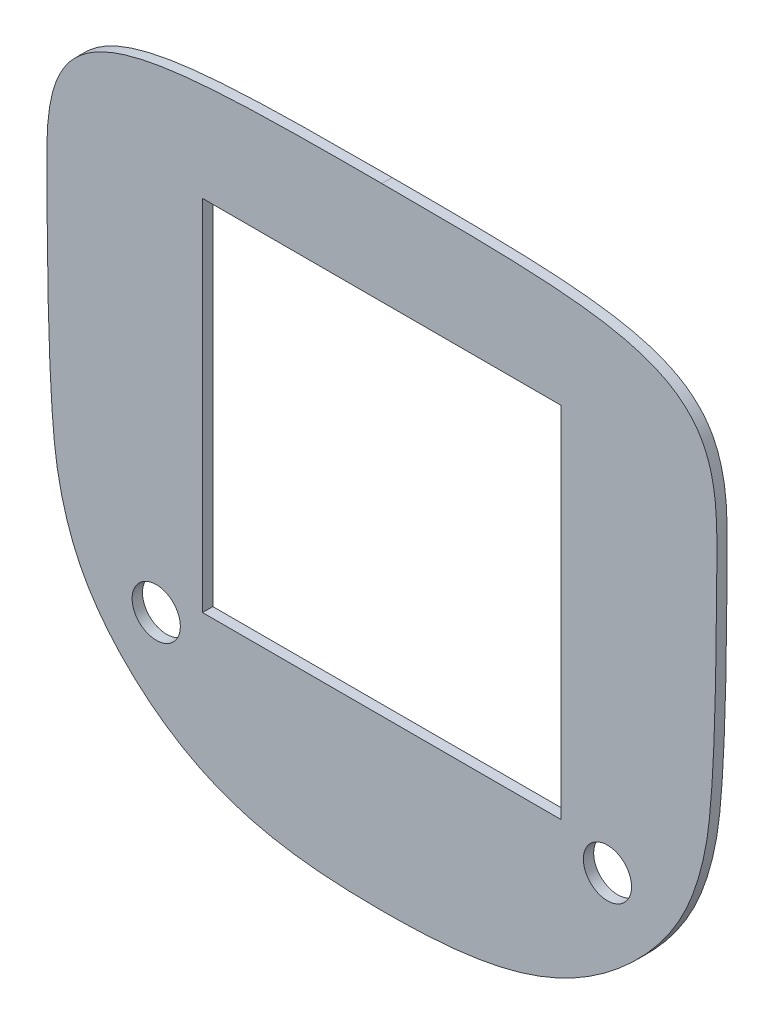
SolidWorks part; units mm, degrees
ref_plane "Front Plane" through (0, 0, 0) normal (0, 0, 1) x (1, 0, 0)
ref_plane "Top Plane" through (0, 0, 0) normal (0, 1, 0) x (1, 0, 0)
ref_plane "Right Plane" through (0, 0, 0) normal (1, 0, 0) x (0, 0, -1)
ref_plane "Plane1" through (0, 0, 100) normal (0, 0, -1) x (-1, 0, 0)
sketch "Sketch1" plane through (0, 0, 100) normal (0, 0, -1) x (-1, 0, 0)
  line L0 (0, 109.7056) -> (0, -73.1371) construction
  line L2 (-52.07, 79.9412) -> (52.07, 79.9412)
  line L3 (-52.07, 79.9412) -> (-52.07, -24.1988)
  line L4 (-52.07, -24.1988) -> (52.07, -24.1988)
  line L5 (52.07, 79.9412) -> (52.07, -24.1988)
  line L6 (-52.07, 79.9412) -> (52.07, -24.1988) construction
  line L7 (-52.07, -24.1988) -> (52.07, 79.9412) construction
  circle A0 centre (-65.5, -30.8878) radius 7
  circle A1 centre (65.5, -30.8878) radius 7
  spline S0 degree 3 poles (120.0442, -3042.1017) (366.3134, 126.0675) (163.9693, -79.8175) (-13.4407, -72.8192) (-16.7834, -72.6088) (-23.4392, -71.9641) (-26.7521, -71.5296) (-33.3376, -70.3562) (-36.61, -69.6165) (-40.6674, -68.4431) (-41.4772, -68.196) (-43.0934, -67.6755) (-43.9008, -67.4017) (-46.31, -66.5418) (-47.8892, -65.9204) (-52.5445, -63.9094) (-55.537, -62.3708) (-61.3063, -58.9085) (-64.0845, -56.9872) (-67.4275, -54.3545) (-68.0901, -53.8159) (-69.3935, -52.723) (-70.0355, -52.1678) (-71.9328, -50.4771) (-73.1598, -49.3164) (-76.728, -45.7341) (-78.9589, -43.2145) (-82.0396, -39.1995) (-83.0214, -37.8212) (-84.8841, -34.9749) (-85.7674, -33.501) (-88.2046, -29.0237) (-89.5634, -25.9428) (-91.2398, -21.1907) (-91.7446, -19.5872) (-92.6604, -16.3463) (-93.0697, -14.7082) (-93.7952, -11.3985) (-94.1118, -9.723) (-94.6517, -6.3658) (-94.8768, -4.683) (-95.2393, -1.3093) (-95.3906, 0.3804) (-95.6676, 3.7621) (-95.7898, 5.4545) (-96.0069, 8.8417) (-96.1016, 10.5367) (-96.2755, 13.928) (-96.3542, 15.6244) (-96.5678, 20.7138) (-96.6807, 24.1076) (-96.9534, 34.291) (-97.0459, 41.0827) (-97.1493, 51.27) (-97.1785, 54.6658) (-97.2277, 59.7595) (-97.2458, 61.4574) (-97.2868, 64.8533) (-97.3103, 66.5515) (-97.2904, 69.9429) (-97.2559, 71.6367) (-97.0958, 75.0177) (-96.9726, 76.705) (-96.5853, 80.0691) (-96.3204, 81.7458) (-95.8548, 83.8317) (-95.7548, 84.2484) (-95.5396, 85.0806) (-95.4241, 85.4969) (-95.0548, 86.7335) (-94.7779, 87.544) (-93.8439, 89.9287) (-93.0837, 91.4561) (-91.9173, 93.2675) (-91.6726, 93.6258) (-91.167, 94.3236) (-90.9058, 94.6639) (-90.0972, 95.6599) (-89.5251, 96.2905) (-88.3172, 97.4873) (-87.6813, 98.0535) (-86.6823, 98.8572) (-86.3418, 99.1176) (-85.6463, 99.6235) (-85.2903, 99.8697) (-83.4921, 101.0547) (-81.9897, 101.864) (-78.8918, 103.2801) (-77.2954, 103.8853) (-74.8499, 104.6822) (-74.0257, 104.9295) (-72.3778, 105.3877) (-71.5521, 105.5993) (-69.0705, 106.1898) (-67.4103, 106.5251) (-64.0815, 107.1133) (-62.4129, 107.3654) (-57.3979, 108.0286) (-54.0423, 108.3496) (-47.3172, 108.8523) (-43.9476, 109.0331) (-37.2, 109.3116) (-33.822, 109.4086) (-27.0609, 109.5527) (-23.6778, 109.5995) (253.3858, 112.2518) (527.5922, 23.6128) (784.5058, 2939.6821) knots -1.59089 -1.59089 -1.59089 -1.59089 0.03125 0.03125 0.0625 0.0625 0.09375 0.09375 0.125 0.125 0.132812 0.132812 0.140625 0.140625 0.15625 0.15625 0.1875 0.1875 0.21875 0.21875 0.226562 0.226562 0.234375 0.234375 0.25 0.25 0.28125 0.28125 0.296875 0.296875 0.3125 0.3125 0.34375 0.34375 0.359375 0.359375 0.375 0.375 0.390625 0.390625 0.40625 0.40625 0.421875 0.421875 0.4375 0.4375 0.453125 0.453125 0.46875 0.46875 0.5 0.5 0.5625 0.5625 0.59375 0.59375 0.609375 0.609375 0.625 0.625 0.640625 0.640625 0.65625 0.65625 0.671875 0.671875 0.675781 0.675781 0.679688 0.679688 0.6875 0.6875 0.703125 0.703125 0.707031 0.707031 0.710938 0.710938 0.71875 0.71875 0.726563 0.726563 0.730469 0.730469 0.734375 0.734375 0.75 0.75 0.765625 0.765625 0.773438 0.773438 0.78125 0.78125 0.796875 0.796875 0.8125 0.8125 0.84375 0.84375 0.875 0.875 0.90625 0.90625 0.9375 0.9375 3.466007 3.466007 3.466007 3.466007 only from (0, -73.1371) to (0, 109.7056)
  spline S1 degree 3 poles (0, -73.1371) (-3.3707, -73.1371) (-6.7344, -73.0838) (-13.4407, -72.8192) (-16.7834, -72.6088) (-23.4392, -71.9641) (-26.7521, -71.5296) (-33.3376, -70.3562) (-36.61, -69.6165) (-40.6674, -68.4431) (-41.4772, -68.196) (-43.0934, -67.6755) (-43.9008, -67.4017) (-46.31, -66.5418) (-47.8892, -65.9204) (-52.5445, -63.9094) (-55.537, -62.3708) (-61.3063, -58.9085) (-64.0845, -56.9872) (-67.4275, -54.3545) (-68.0901, -53.8159) (-69.3935, -52.723) (-70.0355, -52.1678) (-71.9328, -50.4771) (-73.1598, -49.3164) (-76.728, -45.7341) (-78.9589, -43.2145) (-82.0396, -39.1995) (-83.0214, -37.8212) (-84.8841, -34.9749) (-85.7674, -33.501) (-88.2046, -29.0237) (-89.5634, -25.9428) (-91.2398, -21.1907) (-91.7446, -19.5872) (-92.6604, -16.3463) (-93.0697, -14.7082) (-93.7952, -11.3985) (-94.1118, -9.723) (-94.6517, -6.3658) (-94.8768, -4.683) (-95.2393, -1.3093) (-95.3906, 0.3804) (-95.6676, 3.7621) (-95.7898, 5.4545) (-96.0069, 8.8417) (-96.1016, 10.5367) (-96.2755, 13.928) (-96.3542, 15.6244) (-96.5678, 20.7138) (-96.6807, 24.1076) (-96.9534, 34.291) (-97.0459, 41.0827) (-97.1493, 51.27) (-97.1785, 54.6658) (-97.2277, 59.7595) (-97.2458, 61.4574) (-97.2868, 64.8533) (-97.3103, 66.5515) (-97.2904, 69.9429) (-97.2559, 71.6367) (-97.0958, 75.0177) (-96.9726, 76.705) (-96.5853, 80.0691) (-96.3204, 81.7458) (-95.8548, 83.8317) (-95.7548, 84.2484) (-95.5396, 85.0806) (-95.4241, 85.4969) (-95.0548, 86.7335) (-94.7779, 87.544) (-93.8439, 89.9287) (-93.0837, 91.4561) (-91.9173, 93.2675) (-91.6726, 93.6258) (-91.167, 94.3236) (-90.9058, 94.6639) (-90.0972, 95.6599) (-89.5251, 96.2905) (-88.3172, 97.4873) (-87.6813, 98.0535) (-86.6823, 98.8572) (-86.3418, 99.1176) (-85.6463, 99.6235) (-85.2903, 99.8697) (-83.4921, 101.0547) (-81.9897, 101.864) (-78.8918, 103.2801) (-77.2954, 103.8853) (-74.8499, 104.6822) (-74.0257, 104.9295) (-72.3778, 105.3877) (-71.5521, 105.5993) (-69.0705, 106.1898) (-67.4103, 106.5251) (-64.0815, 107.1133) (-62.4129, 107.3654) (-57.3979, 108.0286) (-54.0423, 108.3496) (-47.3172, 108.8523) (-43.9476, 109.0331) (-37.2, 109.3116) (-33.822, 109.4086) (-27.0609, 109.5527) (-23.6778, 109.5995) (-13.5305, 109.6966) (-6.7653, 109.7056) (0, 109.7056) knots 0 0 0 0 0.03125 0.03125 0.0625 0.0625 0.09375 0.09375 0.125 0.125 0.132812 0.132812 0.140625 0.140625 0.15625 0.15625 0.1875 0.1875 0.21875 0.21875 0.226562 0.226562 0.234375 0.234375 0.25 0.25 0.28125 0.28125 0.296875 0.296875 0.3125 0.3125 0.34375 0.34375 0.359375 0.359375 0.375 0.375 0.390625 0.390625 0.40625 0.40625 0.421875 0.421875 0.4375 0.4375 0.453125 0.453125 0.46875 0.46875 0.5 0.5 0.5625 0.5625 0.59375 0.59375 0.609375 0.609375 0.625 0.625 0.640625 0.640625 0.65625 0.65625 0.671875 0.671875 0.675781 0.675781 0.679688 0.679688 0.6875 0.6875 0.703125 0.703125 0.707031 0.707031 0.710938 0.710938 0.71875 0.71875 0.726563 0.726563 0.730469 0.730469 0.734375 0.734375 0.75 0.75 0.765625 0.765625 0.773438 0.773438 0.78125 0.78125 0.796875 0.796875 0.8125 0.8125 0.84375 0.84375 0.875 0.875 0.90625 0.90625 0.9375 0.9375 1 1 1 1
  spline S2 degree 3 poles (0, -73.1371) (3.3707, -73.1371) (6.7344, -73.0838) (13.4407, -72.8192) (16.7834, -72.6088) (23.4392, -71.9641) (26.7521, -71.5296) (33.3376, -70.3562) (36.61, -69.6165) (40.6674, -68.4431) (41.4772, -68.196) (43.0934, -67.6755) (43.9008, -67.4017) (46.31, -66.5418) (47.8892, -65.9204) (52.5445, -63.9094) (55.537, -62.3708) (61.3063, -58.9085) (64.0845, -56.9872) (67.4275, -54.3545) (68.0901, -53.8159) (69.3935, -52.723) (70.0355, -52.1678) (71.9328, -50.4771) (73.1598, -49.3164) (76.728, -45.7341) (78.9589, -43.2145) (82.0396, -39.1995) (83.0214, -37.8212) (84.8841, -34.9749) (85.7674, -33.501) (88.2046, -29.0237) (89.5634, -25.9428) (91.2398, -21.1907) (91.7446, -19.5872) (92.6604, -16.3463) (93.0697, -14.7082) (93.7952, -11.3985) (94.1118, -9.723) (94.6517, -6.3658) (94.8768, -4.683) (95.2393, -1.3093) (95.3906, 0.3804) (95.6676, 3.7621) (95.7898, 5.4545) (96.0069, 8.8417) (96.1016, 10.5367) (96.2755, 13.928) (96.3542, 15.6244) (96.5678, 20.7138) (96.6807, 24.1076) (96.9534, 34.291) (97.0459, 41.0827) (97.1493, 51.27) (97.1785, 54.6658) (97.2277, 59.7595) (97.2458, 61.4574) (97.2868, 64.8533) (97.3103, 66.5515) (97.2904, 69.9429) (97.2559, 71.6367) (97.0958, 75.0177) (96.9726, 76.705) (96.5853, 80.0691) (96.3204, 81.7458) (95.8548, 83.8317) (95.7548, 84.2484) (95.5396, 85.0806) (95.4241, 85.4969) (95.0548, 86.7335) (94.7779, 87.544) (93.8439, 89.9287) (93.0837, 91.4561) (91.9173, 93.2675) (91.6726, 93.6258) (91.167, 94.3236) (90.9058, 94.6639) (90.0972, 95.6599) (89.5251, 96.2905) (88.3172, 97.4873) (87.6813, 98.0535) (86.6823, 98.8572) (86.3418, 99.1176) (85.6463, 99.6235) (85.2903, 99.8697) (83.4921, 101.0547) (81.9897, 101.864) (78.8918, 103.2801) (77.2954, 103.8853) (74.8499, 104.6822) (74.0257, 104.9295) (72.3778, 105.3877) (71.5521, 105.5993) (69.0705, 106.1898) (67.4103, 106.5251) (64.0815, 107.1133) (62.4129, 107.3654) (57.3979, 108.0286) (54.0423, 108.3496) (47.3172, 108.8523) (43.9476, 109.0331) (37.2, 109.3116) (33.822, 109.4086) (27.0609, 109.5527) (23.6778, 109.5995) (13.5305, 109.6966) (6.7653, 109.7056) (0, 109.7056) knots 0 0 0 0 0.03125 0.03125 0.0625 0.0625 0.09375 0.09375 0.125 0.125 0.132812 0.132812 0.140625 0.140625 0.15625 0.15625 0.1875 0.1875 0.21875 0.21875 0.226562 0.226562 0.234375 0.234375 0.25 0.25 0.28125 0.28125 0.296875 0.296875 0.3125 0.3125 0.34375 0.34375 0.359375 0.359375 0.375 0.375 0.390625 0.390625 0.40625 0.40625 0.421875 0.421875 0.4375 0.4375 0.453125 0.453125 0.46875 0.46875 0.5 0.5 0.5625 0.5625 0.59375 0.59375 0.609375 0.609375 0.625 0.625 0.640625 0.640625 0.65625 0.65625 0.671875 0.671875 0.675781 0.675781 0.679688 0.679688 0.6875 0.6875 0.703125 0.703125 0.707031 0.707031 0.710938 0.710938 0.71875 0.71875 0.726563 0.726563 0.730469 0.730469 0.734375 0.734375 0.75 0.75 0.765625 0.765625 0.773438 0.773438 0.78125 0.78125 0.796875 0.796875 0.8125 0.8125 0.84375 0.84375 0.875 0.875 0.90625 0.90625 0.9375 0.9375 1 1 1 1
  point P7 (0, 27.8712)
  dimension "D1" = 14
  dimension "D2" = 104.14
  dimension "D3" = 104.14
extrude "Boss-Extrude1" add sketch "Sketch1" along normal blind 3
